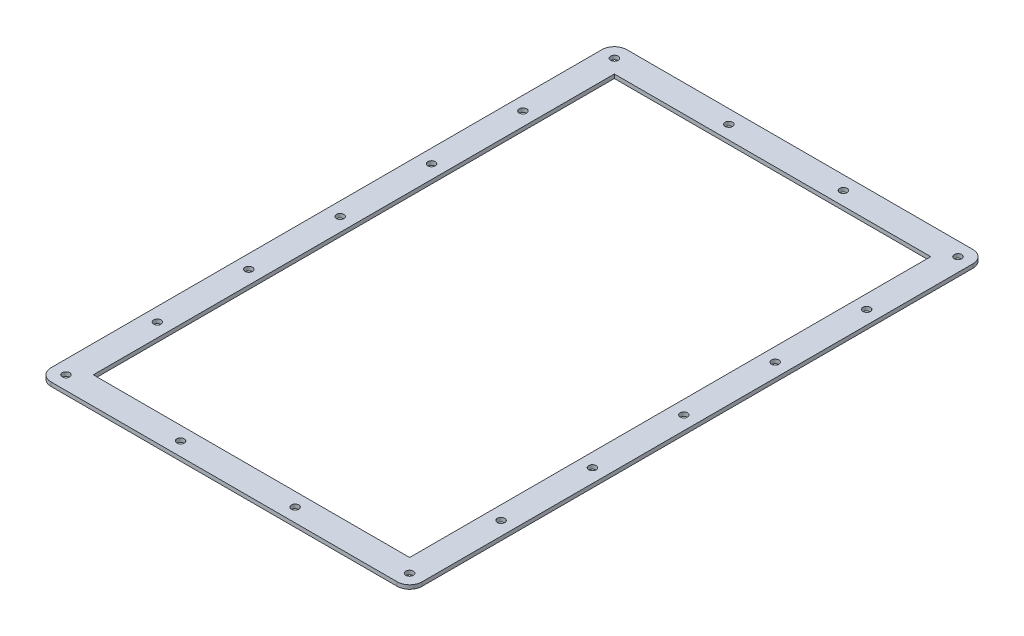
SolidWorks part; units mm, degrees
material "5052-H32"
ref_plane "Front Plane" through (0, 0, 0) normal (0, 0, 1) x (1, 0, 0)
ref_plane "Top Plane" through (0, 0, 0) normal (0, 1, 0) x (1, 0, 0)
ref_plane "Right Plane" through (0, 0, 0) normal (1, 0, 0) x (0, 0, -1)
sketch "Sketch1" plane through (0, 0, 0) normal (0, 1, 0) x (1, 0, 0)
  line L0 (-147, 192) -> (152, 192)
  line L1 (-125, -250) -> (130, -250)
  line L2 (-125, -250) -> (-125, 170)
  line L3 (-125, 170) -> (130, 170)
  line L4 (130, -250) -> (130, 170)
  line L5 (-125, -250) -> (130, 170) construction
  line L6 (-125, 170) -> (130, -250) construction
  line L7 (152, -272) -> (152, 192)
  line L8 (-147, -272) -> (152, -272)
  line L9 (-147, -272) -> (-147, 192)
  line L12 (130, -40) -> (-125, -40) construction
  circle A34 centre (141, 181) radius 3
  circle A35 centre (48.6667, 181) radius 3
  circle A36 centre (-43.6667, 181) radius 3
  circle A37 centre (-136, 181) radius 3
  circle A90 centre (141, 107.3333) radius 3
  circle A91 centre (141, 33.6667) radius 3
  circle A92 centre (141, -40) radius 3
  circle A93 centre (141, -113.6667) radius 3
  circle A94 centre (141, -187.3333) radius 3
  circle A102 centre (-136, 107.3333) radius 3
  circle A103 centre (141, -261) radius 3
  circle A106 centre (-136, 33.6667) radius 3
  circle A107 centre (48.6667, -261) radius 3
  circle A110 centre (-136, -40) radius 3
  circle A111 centre (-43.6667, -261) radius 3
  circle A114 centre (-136, -113.6667) radius 3
  circle A115 centre (-136, -261) radius 3
  circle A118 centre (-136, -187.3333) radius 3
  circle A119 centre (48.6667, -113.6667) radius 3 [skipped]
  circle A120 centre (-43.6667, -113.6667) radius 3 [skipped]
  circle A121 centre (48.6667, 107.3333) radius 3 [skipped]
  circle A122 centre (-43.6667, 107.3333) radius 3 [skipped]
  circle A123 centre (48.6667, 33.6667) radius 3 [skipped]
  circle A124 centre (48.6667, -40) radius 3 [skipped]
  circle A125 centre (-43.6667, -40) radius 3 [skipped]
  circle A126 centre (-43.6667, 33.6667) radius 3 [skipped]
  circle A127 centre (48.6667, -187.3333) radius 3 [skipped]
  circle A128 centre (-43.6667, -187.3333) radius 3 [skipped]
  dimension "D4" = 6
  dimension "D2" = 420
  dimension "D1" = 22
  dimension "D3" = 255
  dimension "D5" = 11
  dimension "D6" = 11
  dimension "D9" = 73.6667
  dimension "D10" = 92.3333
  dimension "D7" = 4
  dimension "D8" = 7
extrude "Boss-Extrude1" add sketch "Sketch1" along normal blind 3.175 contours L9 L8 L7 L0 L4 L1 L2 L3 A34 region at (2.5, 0, -186.4801)
fillet "Fillet1" radius 10 4 edges at (152, 1.5875, 272) (-147, 1.5875, 272) (152, 1.5875, -192) (-147, 1.5875, -192)
equation "\"L\"= 420mm"
equation "\"W\"= 255mm"
equation "\"H\"= 110mm"
equation "\"Compartment Width\"= 80"
equation "\"T\"= 4.7625 * 2 / 3mm"
equation "\"Inside Fillet Radius\"= 5.55625mm"
equation "\"Hole\"=25mm"
equation "\"D2@Sketch1\"=\"L\""
equation "\"D1@Boss-Extrude1\"=\"T\""
equation "\"D3@Sketch1\"=\"W\""
equation "\"D9@Sketch1\"=(\"L\"+22)/6"
equation "\"D10@Sketch1\"=(\"W\"+22)/3"
equation "\"Offset\"= 18mm"
equation "\"Wheel to Wall\"= 43"
